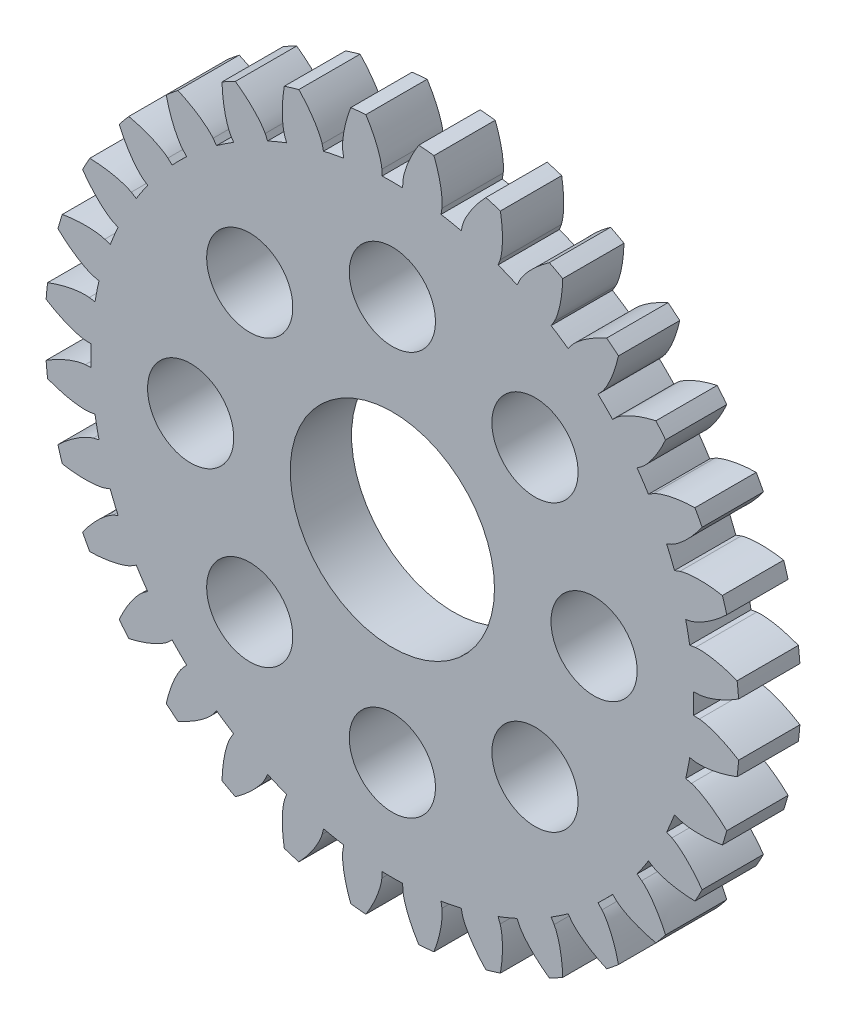
SolidWorks part; units mm, degrees
ref_plane "正面" through (0, 0, 0) normal (0, 0, 1) x (1, 0, 0)
ref_plane "平面" through (0, 0, 0) normal (0, 1, 0) x (1, 0, 0)
ref_plane "右側面" through (0, 0, 0) normal (1, 0, 0) x (0, 0, -1)
sketch "インボリュート スケッチ" plane through (0, 0, 0) normal (0, 0, 1) x (1, 0, 0)
  line L0 (-46.6927, -16.6405) -> (0.5138, -15.0263)
  line L1 (0.5138, -15.0263) -> (-0.5138, 15.0263) construction
  line L2 (0, 0) -> (0, 17) construction
  line L3 (-0.5138, 15.0263) -> (-0.5041, 14.7414)
  line L4 (0, 0) -> (0.5138, -15.0263)
  line L5 (-0.5041, 14.7414) -> (0, 14.7414)
  line L6 (0, 14.7414) -> (0, 0)
  circle A0 centre (0, 0) radius 15.0351 construction
  circle A1 centre (0, 0) radius 16 construction
  circle A2 centre (0, 0) radius 14.75 construction
  circle A3 centre (0, 0) radius 17 construction
  spline S0 degree 4 poles (-0.5138, 15.0263) (-0.5159, 15.0548) (-0.5218, 15.1117) (-0.5404, 15.2246) (-0.5892, 15.4367) (-0.6759, 15.716) (-0.8805, 16.2317) (-1.297, 17.0096) (-1.9931, 17.9739) (-3.1489, 19.1678) (-4.6974, 20.3489) (-6.5672, 21.3886) (-8.717, 22.22) (-10.9518, 22.779) (-13.2347, 23.082) (-15.65, 23.1478) (-18.6332, 22.9171) (-22.1316, 22.1876) (-26.0306, 20.7553) (-30.0637, 18.5141) (-33.7308, 15.7177) (-36.579, 12.8613) (-38.7428, 10.1707) (-40.3547, 7.7903) (-41.5274, 5.812) (-42.8455, 3.2575) (-43.965, 0.6074) (-44.8848, -2.1174) (-45.7495, -5.4571) (-46.2198, -8.0013) (-46.5006, -10.2863) (-46.6451, -12.2894) (-46.6919, -13.3002) (-46.7148, -14.1491) (-46.7213, -14.9318) (-46.7204, -15.5377) (-46.7026, -16.4013) (-46.6795, -17.0436) (-46.6261, -18.1011) (-46.5621, -18.9123) (-46.474, -19.9053) (-46.372, -20.7834) (-46.25, -21.7319) (-46.1122, -22.627) (-45.9948, -23.3298) (-45.9116, -23.7755) (-45.8682, -24.0076) knots 0 0 0 0 0 0.001401 0.002802 0.005604 0.010661 0.015718 0.02996 0.048734 0.068727 0.096889 0.125051 0.153212 0.181374 0.209535 0.237696 0.271429 0.327752 0.384075 0.440398 0.496721 0.553044 0.581206 0.609367 0.637529 0.66569 0.722013 0.750174 0.778336 0.834659 0.84874 0.86282 0.876901 0.883942 0.890982 0.900036 0.909091 0.920455 0.931818 0.943182 0.954545 0.965909 0.977273 0.988636 1 1 1 1 1 construction
  spline S1 degree 4 poles (-0.5138, 15.0263) (-0.5159, 15.0548) (-0.5218, 15.1117) (-0.5404, 15.2246) (-0.5892, 15.4367) (-0.6759, 15.716) (-0.8805, 16.2317) (-1.297, 17.0096) (-1.9931, 17.9739) (-3.1489, 19.1678) (-4.6974, 20.3489) (-6.5672, 21.3886) (-8.717, 22.22) (-10.9518, 22.779) (-13.2347, 23.082) (-15.65, 23.1478) (-18.6332, 22.9171) (-22.1316, 22.1876) (-26.0306, 20.7553) (-30.0637, 18.5141) (-33.7308, 15.7177) (-36.579, 12.8613) (-38.7428, 10.1707) (-40.3547, 7.7903) (-41.5274, 5.812) (-42.8455, 3.2575) (-43.965, 0.6074) (-44.8848, -2.1174) (-45.7495, -5.4571) (-46.2198, -8.0013) (-46.5006, -10.2863) (-46.6451, -12.2894) (-46.6919, -13.3002) (-46.7148, -14.1491) (-46.7213, -14.9318) (-46.7204, -15.5377) (-46.7081, -16.1325) (-46.6984, -16.4727) (-46.6927, -16.6405) knots 0 0 0 0 0 0.001401 0.002802 0.005604 0.010661 0.015718 0.02996 0.048734 0.068727 0.096889 0.125051 0.153212 0.181374 0.209535 0.237696 0.271429 0.327752 0.384075 0.440398 0.496721 0.553044 0.581206 0.609367 0.637529 0.66569 0.722013 0.750174 0.778336 0.834659 0.84874 0.86282 0.876901 0.883942 0.890982 0.900036 0.909091 0.909091 0.909091 0.909091 0.909091
  point P6 (-0.7851, 15.9807)
  point P12 (0, 16)
  point P24 (0, 0)
  dimension "D1" = 30.0702
  dimension "D2" = 32
  dimension "D3" = 29.5
  dimension "D4" = 34
  dimension "D5" = 0.7854
extrude "インボリュート ボス" add sketch "インボリュート スケッチ" along normal blind 3 contours S1 L0 L4 region at (-21.138, 1.3292, 0)
mirror "インボリュート ミラー" about plane through (0, 0, 3) normal (1, 0, 0) of bodies 161
sketch "歯先円 スケッチ" plane through (0, 0, 3) normal (0, 0, 1) x (1, 0, 0)
  circle A0 centre (0, 0) radius 49.5693
  circle A1 centre (0, 0) radius 17
  dimension "D1" = 34
extrude "歯先円 カット" cut sketch "歯先円 スケッチ" against normal through all
sketch "歯分割 スケッチ" plane through (0, 0, 3) normal (0, 0, 1) x (1, 0, 0)
  line L0 (-1.6663, 16.9181) -> (0, 0)
  line L1 (0, 0) -> (1.6663, 16.9181)
  line L2 (0, 0) -> (0, 16) construction
  arc A0 (-1.6663, 16.9181) -> (1.6663, 16.9181) centre (0, 0) ccw
  circle A2 centre (0, 0) radius 16 construction
  arc A3 (-1.2962, 16.9505) -> (-7.4154, -15.2974) centre (0, 0) ccw construction
  point P9 (-1.5683, 15.923)
  point P10 (1.5683, 15.923)
  dimension "D1" = 32
  dimension "D2" = 3.1416
extrude "歯分割 カット" cut sketch "歯分割 スケッチ" against normal through all
pattern_circular "歯分割 円形コピー" count 32 over 360 about axis through (0, 0, 0) along (0, 0, 1) of bodies 166
sketch "歯底円 スケッチ" plane through (0, 0, 3) normal (0, 0, 1) x (1, 0, 0)
  circle A0 centre (0, 0) radius 14.75
  dimension "D1" = 29.5
extrude "歯底円 ボス" add sketch "歯底円 スケッチ" against normal through all
sketch "軸 丸穴 スケッチ" plane through (0, 0, 3) normal (0, 0, 1) x (1, 0, 0)
  circle A0 centre (0, 0) radius 5
  dimension "D1" = 10
extrude "軸 丸穴 カット" cut sketch "軸 丸穴 スケッチ" against normal through all
sketch "軸 キー溝 スケッチ" plane through (0, 0, 3) normal (0, 0, 1) x (1, 0, 0)
  line L2 (-1.5, 3.7081) -> (-1.5, 5.4)
  line L3 (-1.5, 5.4) -> (1.5, 5.4)
  line L4 (1.5, 3.7081) -> (1.5, 5.4)
  arc A0 (-1.5, 3.7081) -> (1.5, 3.7081) centre (0, 0) ccw
  dimension "D1" = 8
  dimension "D2" = 3
  dimension "D3" = 5.4
extrude "軸 キー溝 カット" [suppressed] cut sketch "軸 キー溝 スケッチ" against normal through all
sketch "軸 Dカット スケッチ" plane through (0, 0, 3) normal (0, 0, 1) x (1, 0, 0)
  line L0 (-2.3958, 3) -> (2.3958, 3)
  arc A0 (-2.828, 2.8289) -> (2.828, 2.8289) centre (0, 0) ccw
  arc A1 (-2.3958, 3) -> (-2.828, 2.8289) centre (-2.6458, 3) ccw
  arc A2 (2.828, 2.8289) -> (2.3958, 3) centre (2.6458, 3) ccw
  dimension "D1" = 8
  dimension "D3" = 0.5
  dimension "D2" = 3
extrude "軸 Dカット カット" [suppressed] cut sketch "軸 Dカット スケッチ" against normal through all
sketch "軸 角穴 スケッチ" plane through (0, 0, 3) normal (0, 0, 1) x (1, 0, 0)
  line L0 (-5.1, 5.1) -> (5.1, 5.1)
  line L1 (-5, -5) -> (5, -5) construction
  line L2 (-5, -5) -> (-5, 5) construction
  line L3 (-5, 5) -> (5, 5) construction
  line L4 (5, -5) -> (5, 5) construction
  line L5 (-5, -5) -> (5, 5) construction
  line L6 (-5, 5) -> (5, -5) construction
  line L7 (5.1, -5.1) -> (5.1, 5.1)
  line L8 (-5.1, -5.1) -> (5.1, -5.1)
  line L9 (-5.1, -5.1) -> (-5.1, 5.1)
  point P0 (0, 0)
  dimension "D1" = 10
  dimension "D2" = 0.1
extrude "軸 角穴 カット" [suppressed] cut sketch "軸 角穴 スケッチ" against normal through all
sketch "フランジ穴 スケッチ" plane through (0, 0, 3) normal (0, 0, 1) x (1, 0, 0)
  circle A0 centre (0, 12) radius 1.6
  circle A1 centre (12, 0) radius 1.6
  circle A2 centre (0, -12) radius 1.6
  circle A3 centre (-12, 0) radius 1.6
  point P12 (0, 0)
  dimension "D2" = 3.2
  dimension "D3" = 12
  dimension "D1" = 4
extrude "フランジ穴 カット" [suppressed] cut sketch "フランジ穴 スケッチ" against normal through all
sketch "合致用スケッチ" plane through (0, 0, 3) normal (0, 0, 1) x (1, 0, 0)
  line L0 (0, 0) -> (0, 16)
  line L1 (0, 0) -> (1.5683, 15.923)
  circle A2 centre (0, 0) radius 16
  dimension "D1" = 32
  dimension "D2" = 5.625
sketch "ｽｹｯﾁ2" plane through (0, 0, 0) normal (0, 0, -1) x (-1, 0, 0)
  line L0 (0, -5) -> (0, -14.75) construction
  line L1 (-3.5355, -3.5355) -> (-10.4298, -10.4298) construction
  line L2 (-5, 0) -> (-14.75, 0) construction
  line L3 (-3.5355, 3.5355) -> (-10.4298, 10.4298) construction
  line L4 (0, 5) -> (0, 14.75) construction
  line L5 (3.5355, 3.5355) -> (10.4298, 10.4298) construction
  line L6 (5, 0) -> (14.75, 0) construction
  line L7 (3.5355, -3.5355) -> (10.4298, -10.4298) construction
  circle A0 centre (0, 0) radius 5 construction
  arc A1 (-0.5041, -14.7414) -> (0.5041, -14.7414) centre (0, 0) ccw construction
  circle A2 centre (0, -9.875) radius 2.1098
  circle A3 centre (-6.9827, -6.9827) radius 2.1098
  circle A4 centre (-9.875, 0) radius 2.1098
  circle A5 centre (-6.9827, 6.9827) radius 2.1098
  circle A6 centre (0, 9.875) radius 2.1098
  circle A7 centre (6.9827, 6.9827) radius 2.1098
  circle A8 centre (9.875, 0) radius 2.1098
  circle A9 centre (6.9827, -6.9827) radius 2.1098
  point P40 (0, 0)
  dimension "D1" = 4.2195
  dimension "D2" = 8
extrude "ｶｯﾄ - 押し出し1" cut sketch "ｽｹｯﾁ2" against normal through all
equation "\"モジュール\"= 1"
equation "\"基準圧力角\"= 20"
equation "\"歯数\"= 32"
equation "\"基準円直径\"= \"歯数\" * \"モジュール\""
equation "\"基礎円直径\"= \"基準円直径\" * cos ( \"基準圧力角\" )"
equation "\"歯先円直径\"= \"基準円直径\" + 2 * \"モジュール\""
equation "\"歯底円直径\"= \"基準円直径\" - 2.5 * \"モジュール\""
equation "\"D1@インボリュート スケッチ\" = \"基礎円直径\""
equation "\"D2@インボリュート スケッチ\" = \"基準円直径\""
equation "\"D3@インボリュート スケッチ\" = \"歯底円直径\""
equation "\"D4@インボリュート スケッチ\" = \"歯先円直径\""
equation "\"D5@インボリュート スケッチ\" = Pi * \"モジュール\" / 4"
equation "\"D1@歯先円 スケッチ\" = \"歯先円直径\""
equation "\"D1@歯分割 スケッチ\" = \"基準円直径\""
equation "\"D2@歯分割 スケッチ\" = PI * \"モジュール\""
equation "\"D1@歯分割 円形コピー\" = \"歯数\""
equation "\"D1@歯底円 スケッチ\" = \"歯底円直径\""
equation "\"板厚\"= 3"
equation "\"D1@インボリュート ボス\"=\"板厚\""
equation "\"D1@合致用スケッチ\" = \"基準円直径\""
equation "\"D2@合致用スケッチ\"=180/\"歯数\""
